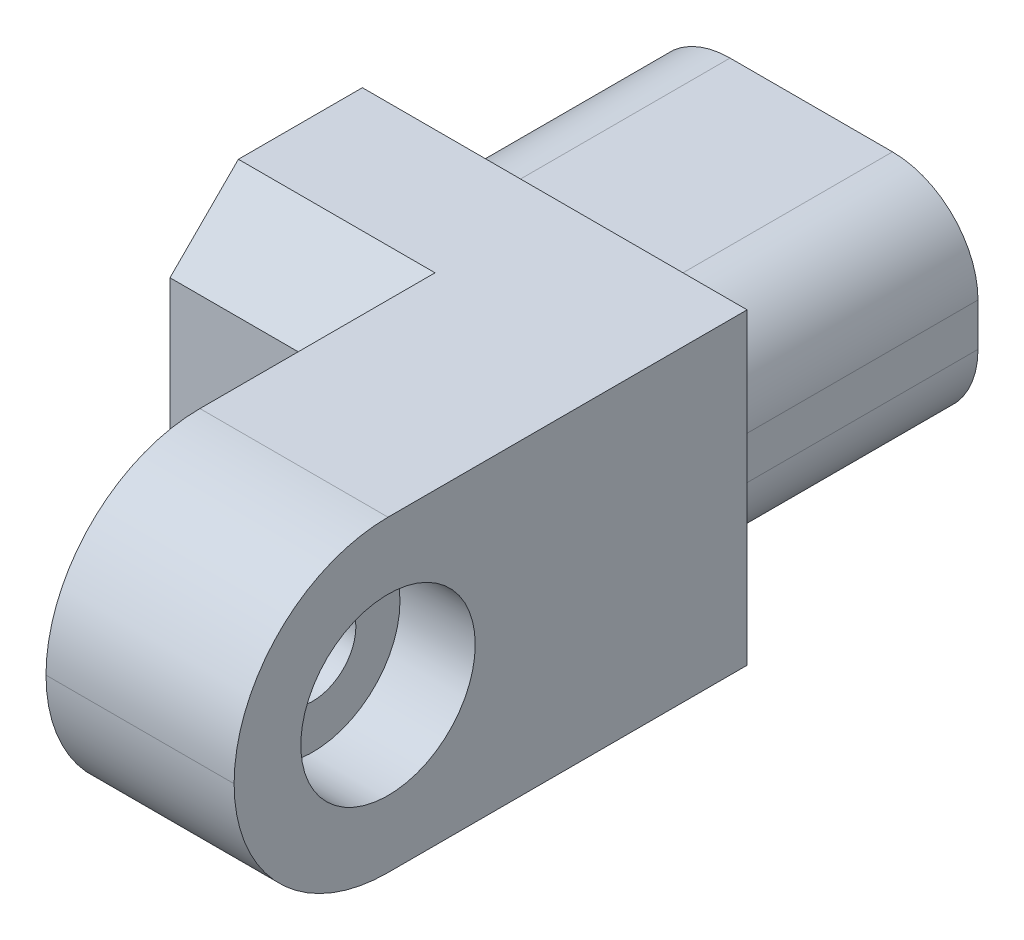
SolidWorks part; units mm, degrees
other "Markup1"
sketch "Sketch6" plane through (14.2875, 11.43, 38.1) normal (0.2973, 0.9472, 0.1204) x (0.8011, -0.1788, -0.5712)
ref_plane "Plan de face" through (0, 0, 0) normal (0, 0, 1) x (1, 0, 0)
ref_plane "Plan de dessus" through (0, 0, 0) normal (0, 1, 0) x (1, 0, 0)
ref_plane "Plan de droite" through (0, 0, 0) normal (1, 0, 0) x (0, 0, -1)
sketch "Sketch2" plane through (0, 0, 0) normal (0, 0, 1) x (1, 0, 0)
  line L1 (12.3825, -7.9375) -> (-12.3825, -7.9375)
  line L2 (12.3825, -7.9375) -> (12.3825, 7.9375)
  line L3 (12.3825, 7.9375) -> (-12.3825, 7.9375)
  line L4 (-12.3825, -7.9375) -> (-12.3825, 7.9375)
  line L5 (12.3825, -7.9375) -> (-12.3825, 7.9375) construction
  line L6 (12.3825, 7.9375) -> (-12.3825, -7.9375) construction
  point P0 (0, 0)
  dimension "D1" = 24.765
  dimension "D2" = 15.875
extrude "Boss-Extrude1" add sketch "Sketch2" against normal blind 19.05
sketch "Sketch3" plane through (0, 0, 0) normal (0, 0, 1) x (1, 0, 0)
  line L1 (14.2875, -11.43) -> (-14.2875, -11.43)
  line L2 (14.2875, -11.43) -> (14.2875, 11.43)
  line L3 (14.2875, 11.43) -> (-14.2875, 11.43)
  line L4 (-14.2875, -11.43) -> (-14.2875, 11.43)
  line L5 (14.2875, -11.43) -> (-14.2875, 11.43) construction
  line L6 (14.2875, 11.43) -> (-14.2875, -11.43) construction
  point P0 (0, 0)
  dimension "D1" = 28.575
  dimension "D2" = 22.86
extrude "Boss-Extrude2" add sketch "Sketch3" along normal blind 38.1
sketch "Sketch4" plane through (0, -11.43, 0) normal (0, -1, 0) x (-1, 0, 0)
  line L0 (14.2875, -38.1) -> (-14.2875, -38.1) construction
  line L5 (14.2875, -38.1) -> (-0.3175, -38.1)
  line L6 (14.2875, -38.1) -> (14.2875, -14.2875)
  line L7 (14.2875, -14.2875) -> (-0.3175, -14.2875)
  line L8 (-0.3175, -38.1) -> (-0.3175, -14.2875)
  line L9 (-14.2875, -38.1) -> (-14.2875, 0) construction
  line L10 (14.2875, -38.1) -> (14.2875, 0) construction
  dimension "D2" = 23.8125
  dimension "D5" = 13.97
extrude "Cut-Extrude1" cut sketch "Sketch4" against normal through all
fillet "Fillet5" radius 11.43 2 edges at (7.3025, -11.43, 38.1) (7.3025, 11.43, 38.1)
fillet "Fillet3" radius 6.35 4 edges at (-12.3825, -7.9375, -9.525) (-12.3825, 7.9375, -9.525) (12.3825, -7.9375, -9.525) (12.3825, 7.9375, -9.525)
chamfer "Chamfer1" distance 5.08 angle 45 2 edges at (-6.985, -11.43, 14.2875) (-6.985, 11.43, 14.2875)
hole_wizard "CBORE for 1/4 Fillister Head Machine Screw1" positions "3DSketch1" profile "Sketch5" counterbore size "1/4" standard "ANSI Inch" end condition up to next
sketch3d "3DSketch1"
  point P0 (14.2875, 0, 26.67)
sketch "Sketch5" plane through (14.2875, 0, 26.67) normal (0, 1, 0) x (0, 0, -1)
  line L0 (0, 0) -> (0, 13.97)
  line L1 (0, 13.97) -> (3.2004, 13.97)
  line L3 (3.2004, 13.97) -> (3.2004, 5.588)
  line L4 (3.2004, 5.588) -> (6.477, 5.588)
  line L5 (6.477, 5.588) -> (6.477, 0)
  line L7 (6.477, 0) -> (0, 0)
  line L11 (0, -6.35) -> (0, 107.95) construction
  dimension "Thru Hole Dia." = 6.4008
  dimension "Thru Hole Depth" = 13.97
  dimension "C'Bore Dia." = 12.954
  dimension "C'Bore Depth" = 5.588
ref_plane "Plane1" through (6.985, 0, 0) normal (1, 0, 0) x (0, 0, -1)
mirror "Mirror1" about plane through (6.985, 0, 0) normal (1, 0, 0) of "CBORE for 1/4 Fillister Head Machine Screw1"
